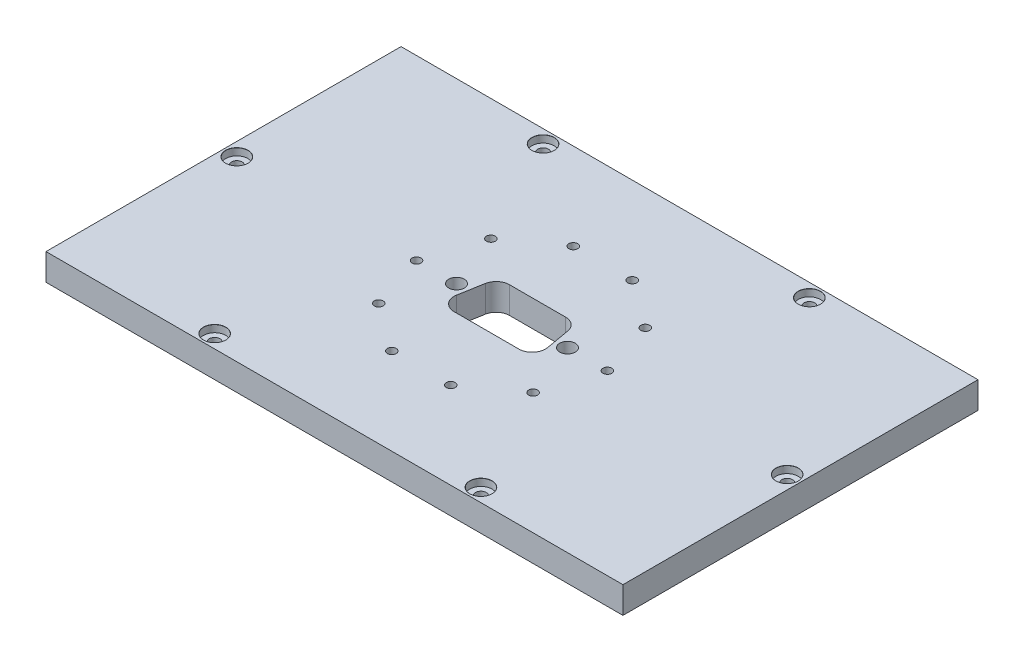
SolidWorks part; units mm, degrees
ref_plane "Ebene vorne" through (0, 0, 0) normal (0, 0, 1) x (1, 0, 0)
ref_plane "Ebene oben" through (0, 0, 0) normal (0, 1, 0) x (1, 0, 0)
ref_plane "Ebene rechts" through (0, 0, 0) normal (1, 0, 0) x (0, 0, -1)
sketch "Skizze1" plane through (0, 0, 0) normal (0, 1, 0) x (1, 0, 0)
  line L1 (0, 0) -> (130, 0)
  line L2 (0, 0) -> (0, 80)
  line L3 (0, 80) -> (130, 80)
  line L4 (130, 0) -> (130, 80)
  dimension "D1" = 80
  dimension "D2" = 130
extrude "Aufsatz-Linear austragen1" add sketch "Skizze1" along normal blind 6
hole_wizard "Ø2.4 (2.4) Durchmesser Bohrung1" positions "Skizze2" profile "Skizze3" hole size "Ø2.4" standard "DIN"
sketch "Skizze2" plane through (0, 6, 0) normal (0, 1, 0) x (1, 0, 0)
  line L0 (130, 80) -> (0, 80) construction
  line L1 (130, 0) -> (130, 80) construction
  line L2 (0, -3.3) -> (0, 3.3) construction
  line L3 (-3.3, 0) -> (3.3, 0) construction
  point P0 (35, 77)
  point P2 (95, 77)
  point P4 (127, 40)
  point P6 (95, 3)
  point P8 (35, 3)
  point P10 (3, 40)
  point P21 (133.0887, 32.8034)
  dimension "D1" = 3
  dimension "D2" = 3
  dimension "D3" = 3
  dimension "D4" = 3
  dimension "D5" = 3
  dimension "D6" = 3
  dimension "D7" = 35
  dimension "D8" = 35
  dimension "D9" = 35
  dimension "D10" = 35
  dimension "D11" = 40
  dimension "D12" = 40
sketch "Skizze3" plane through (35, 6, -77) normal (1, 0, 0) x (0, 0, 1)
  line L0 (0, 0) -> (0, 10.721)
  line L1 (0, 10.721) -> (1.2, 10)
  line L2 (1.2, 10) -> (1.2, 0.025)
  line L3 (1.2, 0.025) -> (1.225, 0)
  line L5 (1.225, 0) -> (0, 0)
  line L6 (-1.2, 0.025) -> (-1.225, 0) construction
  line L10 (0, 10.721) -> (-1.2, 10) construction
  line L11 (0, -6.35) -> (0, 107.95) construction
  dimension "Bohrerdurchmesser" = 2.4
  dimension "Bohrungstiefe" = 10
  dimension "Senkdurchmesser2 (Oben)" = 2.45
  dimension "Senkwinkel2 (Oben)" = 90
  dimension "Spitzenwinkel" = 118
hole_wizard "Stirnsenkung für M2 Flachkopfschraube mit Schlitz1" positions "Skizze6" profile "Skizze7" counterbore size "M2" standard "DIN"
sketch "Skizze6" plane through (0, 6, 0) normal (0, 1, 0) x (1, 0, 0)
  point P0 (95, 3)
  point P3 (127, 40)
  point P6 (95, 77)
  point P9 (35, 77)
  point P12 (3, 40)
  point P15 (35, 3)
sketch "Skizze7" plane through (95, 6, -3) normal (1, 0, 0) x (0, 0, 1)
  line L0 (0, 0) -> (0, 2.721)
  line L1 (0, 2.721) -> (1.2, 2)
  line L2 (1.2, 2) -> (1.2, 1.6)
  line L3 (1.2, 1.6) -> (2.5, 1.6)
  line L5 (2.5, 1.6) -> (2.5, 0.025)
  line L6 (2.5, 0.025) -> (2.525, 0)
  line L7 (2.525, 0) -> (0, 0)
  line L8 (-2.5, 0.025) -> (-2.525, 0) construction
  line L10 (0, 2.721) -> (-1.2, 2) construction
  line L11 (0, -6.35) -> (0, 107.95) construction
  dimension "Bohrerdurchmesser" = 2.4
  dimension "Bohrungstiefe" = 2
  dimension "Senkdurchmesser2" = 5
  dimension "Senktiefe2" = 1.6
  dimension "Senkdurchmesser4 (Oben)" = 5.05
  dimension "Senkwinkel2 (Oben)" = 90
  dimension "Spitzenwinkel" = 118
sketch "Skizze8" plane through (0, 6, 0) normal (0, 1, 0) x (1, 0, 0)
  line L0 (65, -24.4296) -> (65, 94.5281) construction
  line L1 (130, 0) -> (130, 80) construction
  line L2 (72.2956, 34.25) -> (57.7044, 34.25)
  line L3 (0, 80) -> (0, 0) construction
  line L4 (147.1504, 40) -> (-23.042, 40) construction
  line L5 (0, 0) -> (130, 0) construction
  line L6 (130, 80) -> (0, 80) construction
  line L7 (54.75, 37.7709) -> (55.7198, 43.2709)
  line L8 (58.6742, 45.75) -> (71.3258, 45.75)
  line L9 (74.2802, 43.2709) -> (75.25, 37.7709)
  circle A1 centre (47.6061, 52.6374) radius 1
  circle A2 centre (58.3561, 60.4477) radius 1
  circle A3 centre (71.6439, 60.4477) radius 1
  circle A4 centre (82.3939, 52.6374) radius 1
  circle A5 centre (86.5, 40) radius 1
  circle A6 centre (82.3939, 27.3626) radius 1
  circle A7 centre (71.6439, 19.5523) radius 1
  circle A8 centre (58.3561, 19.5523) radius 1
  circle A9 centre (47.6061, 27.3626) radius 1
  circle A10 centre (43.5, 40) radius 1
  arc A11 (57.7044, 34.25) -> (54.75, 37.7709) centre (57.7044, 37.25) cw
  arc A12 (55.7198, 43.2709) -> (58.6742, 45.75) centre (58.6742, 42.75) cw
  arc A13 (71.3258, 45.75) -> (74.2802, 43.2709) centre (71.3258, 42.75) cw
  arc A14 (75.25, 37.7709) -> (72.2956, 34.25) centre (72.2956, 37.25) cw
  circle A15 centre (77.5, 40) radius 1.75
  circle A16 centre (52.5, 40) radius 1.75
  point P14 (65, 40)
  dimension "D1" = 2
  dimension "D3" = 43
  dimension "D4" = 3
  dimension "D6" = 11.5
  dimension "D7" = 3
  dimension "D9" = 25
  dimension "D10" = 3.5
  dimension "D5" = 20.5
  dimension "D8" = 80
  dimension "D2" = 10
extrude "Schnitt-Linear austragen1" cut sketch "Skizze8" against normal up to surface (6 mm away) up to face at (35, 0, -78.2)
